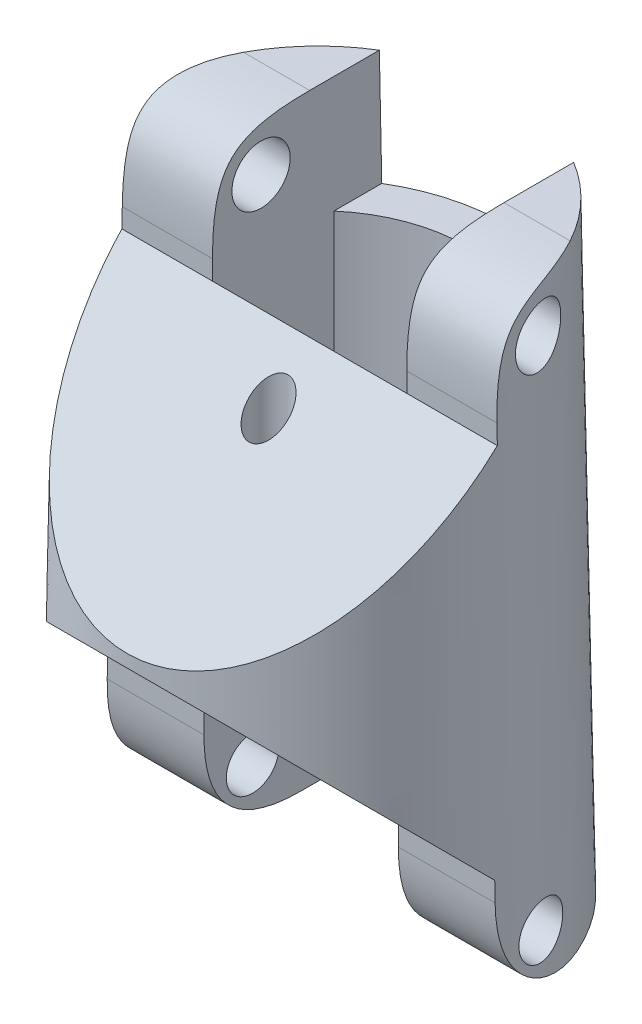
SolidWorks part; units mm, degrees
material "ABS"
ref_plane "Front Plane" through (0, 0, 0) normal (0, 0, 1) x (1, 0, 0)
ref_plane "Top Plane" through (0, 0, 0) normal (0, 1, 0) x (1, 0, 0)
ref_plane "Right Plane" through (0, 0, 0) normal (1, 0, 0) x (0, 0, -1)
sketch "Sketch1" plane through (0, 0, 0) normal (0, 1, 0) x (1, 0, 0)
  circle A0 centre (0, 0) radius 10
  dimension "D1" = 20
extrude "Boss-Extrude1" add sketch "Sketch1" along normal blind 25 draft 1 and the other way blind 6 draft 1
sketch "Sketch2" plane through (0, 0, 0) normal (1, 0, 0) x (0, 0, -1)
  line L0 (-0.4364, 25) -> (-0.4364, 19)
  line L2 (9.5636, 25) -> (-9.5636, 25) construction
  line L3 (-0.4364, 19) -> (-12.6798, 6.7566)
  line L5 (-12.6798, 6.7566) -> (-12.6798, 25)
  line L6 (-12.6798, 25) -> (-0.4364, 25)
  dimension "D1" = 10
  dimension "D2" = 6
  dimension "D3" = 135
extrude "Cut-Extrude1" cut sketch "Sketch2" against normal through all both and the other way through all
sketch "Sketch3" plane through (0, 0, 0.4364) normal (0, 0, 1) x (1, 0, 0)
  line L0 (-9.6585, 19) -> (9.6585, 19) construction
  line L1 (5, 25) -> (-5, 25)
  line L2 (5, 25) -> (5, 19)
  line L3 (5, 19) -> (-5, 19)
  line L4 (-5, 25) -> (-5, 19)
  line L5 (5, 25) -> (-5, 19) construction
  line L6 (5, 19) -> (-5, 25) construction
  point P0 (0, 22)
  dimension "D1" = 10
  dimension "D2" = 6
extrude "Cut-Extrude2" cut sketch "Sketch3" against normal blind 25
sketch "Sketch4" plane through (-5, 0, 0) normal (1, 0, 0) x (0, 0, -1)
  circle A0 centre (2.0636, 22.5) radius 1.5
  dimension "D3" = 3
  dimension "D1" = 2.5
  dimension "D2" = 2.5
extrude "Cut-Extrude3" cut sketch "Sketch4" against normal through all both and the other way through all
fillet "Fillet2" radius 5 2 edges at (7.2768, 25, 0.4364) (-7.2768, 25, 0.4364)
sketch "Sketch7" plane through (0, 0, 0) normal (1, 0, 0) x (0, 0, -1)
  line L0 (-0.873, -6) -> (-0.873, 0)
  line L1 (-10.1047, -6) -> (10.1047, -6) construction
  line L2 (-0.873, 0) -> (-11.3178, 10.4448)
  line L3 (-11.3178, 10.4448) -> (-11.3178, -6)
  line L4 (-11.3178, -6) -> (-0.873, -6)
  dimension "D1" = 6
  dimension "D2" = 135
extrude "Cut-Extrude5" cut sketch "Sketch7" against normal through all both and the other way through all
sketch "Sketch8" plane through (0, 0, 0.873) normal (0, 0, 1) x (1, 0, 0)
  line L0 (-9.9618, 0) -> (9.9618, 0) construction
  line L1 (-5, -6) -> (5, -6)
  line L2 (-5, -6) -> (-5, 0)
  line L3 (-5, 0) -> (5, 0)
  line L4 (5, -6) -> (5, 0)
  line L5 (-5, -6) -> (5, 0) construction
  line L6 (-5, 0) -> (5, -6) construction
  point P0 (0, -3)
  dimension "D1" = 6
  dimension "D2" = 10
  dimension "D3" = 0
extrude "Cut-Extrude6" cut sketch "Sketch8" against normal through all
sketch "Sketch6" plane through (0, 19, 0) normal (0, 1, 0) x (1, 0, 0)
  line L0 (5, 8.2751) -> (5, -0.4364) construction
  line L1 (-5, -0.4364) -> (5, -0.4364) construction
  line L2 (-5, 8.2751) -> (-5, -0.4364) construction
  line L3 (5, 5.8141) -> (5, -0.4364)
  line L4 (-5, -0.4364) -> (5, -0.4364)
  line L5 (-5, 5.8141) -> (-5, -0.4364)
  arc A3 (3.9657, 6.5633) -> (-3.9657, 6.5633) centre (0, 0) ccw
  arc A4 (5, 5.8141) -> (-5, 5.8141) centre (0, 0) ccw
  dimension "D1" = 2
extrude "Cut-Extrude7" cut sketch "Sketch6" against normal through all contours A4 L5 L4 L3
sketch "Sketch9" plane through (-5, 0, 0) normal (1, 0, 0) x (0, 0, -1)
  circle A0 centre (1.627, -3.5) radius 1.3515
  dimension "D1" = 2.5
  dimension "D2" = 2.5
extrude "Cut-Extrude8" cut sketch "Sketch9" against normal through all both and the other way through all
fillet "Fillet3" radius 5 2 edges at (7.5335, -6, 0.873) (-7.5335, -6, 0.873)
sketch "Sketch10" plane through (0, 19, 0) normal (0, 1, 0) x (1, 0, 0)
  circle A0 centre (0, -2.5503) radius 1
extrude "Cut-Extrude9" cut sketch "Sketch10" against normal through all
